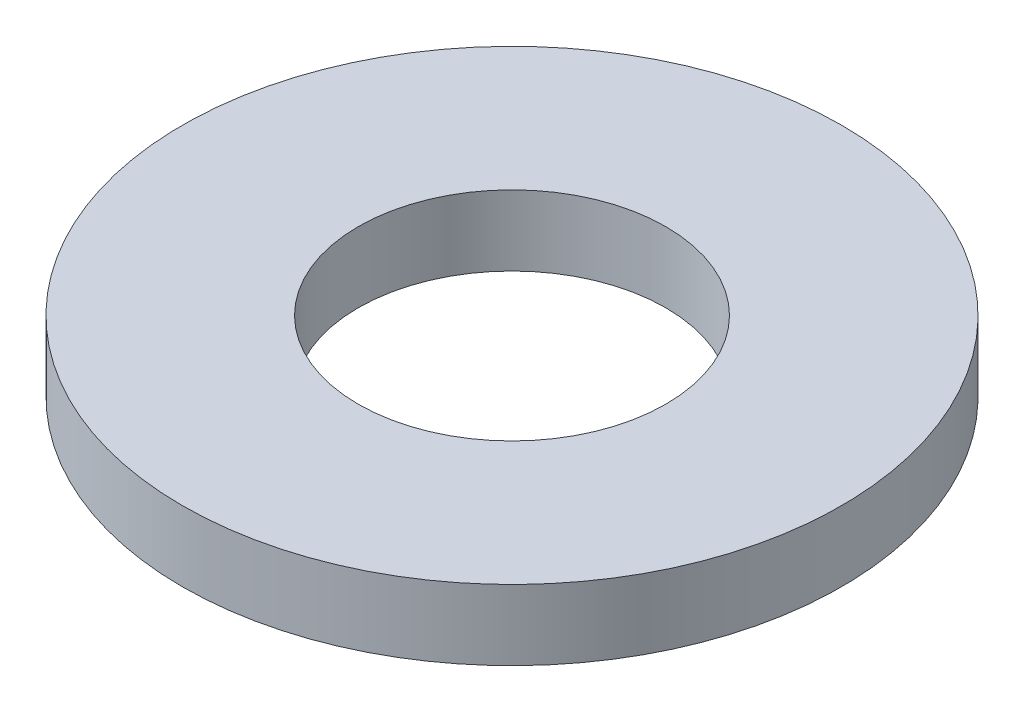
SolidWorks part; units mm, degrees
ref_plane "Front Plane" through (0, 0, 0) normal (0, 0, 1) x (1, 0, 0)
ref_plane "Top Plane" through (0, 0, 0) normal (0, 1, 0) x (1, 0, 0)
ref_plane "Right Plane" through (0, 0, 0) normal (1, 0, 0) x (0, 0, -1)
sketch "Sketch1" plane through (0, 0, 0) normal (0, 1, 0) x (1, 0, 0)
  circle A0 centre (0, 0) radius 37.5
  dimension "FLANGE_OD" = 75
extrude "Boss-Extrude1" add sketch "Sketch1" along normal blind 8
sketch "Sketch2" plane through (0, 0, 0) normal (0, 1, 0) x (1, 0, 0)
  circle A0 centre (0, 0) radius 17.5
  dimension "BORE_D" = 35
extrude "Cut-Extrude1" cut sketch "Sketch2" along normal through all
sketch "Sketch3" plane through (0, 8, 0) normal (0, 1, 0) x (1, 0, 0)
  circle A0 centre (0, 0) radius 11.9709 construction
  circle A1 centre (-11.9709, 0) radius 1.6944
  dimension "BOLT_D" = 3.3888
  dimension "BOLT_PCD" = 23.9419
extrude "Cut-Extrude2" cut sketch "Sketch3" against normal blind 5.93 rebuild error yes
pattern_circular "CirPattern1" count 5 over 360 rebuild error yes
